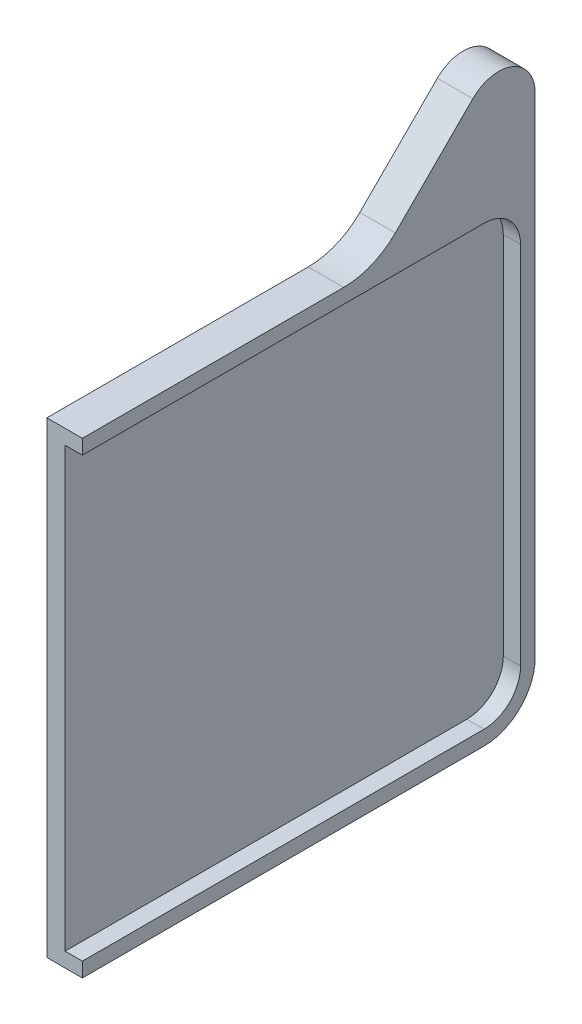
SolidWorks part; units mm, degrees
ref_plane "Front Plane" through (0, 0, 0) normal (0, 0, 1) x (1, 0, 0)
ref_plane "Top Plane" through (0, 0, 0) normal (0, 1, 0) x (1, 0, 0)
ref_plane "Right Plane" through (0, 0, 0) normal (1, 0, 0) x (0, 0, -1)
sketch "Sketch1" plane through (35.1028, 0, 0) normal (-1, 0, 0) x (0, 0, 1)
  line L0 (-114.3, 38.1) -> (-114.3, -38.1)
  line L1 (-114.3, 38.1) -> (-184.15, 38.1)
  line L2 (-190.5, 31.75) -> (-190.5, -31.75)
  line L3 (-184.15, -38.1) -> (-114.3, -38.1)
  line L4 (190.5, -31.75) -> (190.5, 31.75)
  line L5 (184.15, 38.1) -> (-184.15, 38.1)
  line L6 (-190.5, 31.75) -> (-190.5, -31.75)
  line L7 (-184.15, -38.1) -> (184.15, -38.1)
  line L8 (190.5, -31.75) -> (190.5, 31.75) construction
  line L9 (184.15, 38.1) -> (-184.15, 38.1) construction
  line L10 (-190.5, 31.75) -> (-190.5, -31.75) construction
  line L11 (-184.15, -38.1) -> (184.15, -38.1) construction
  arc A0 (-190.5, -31.75) -> (-184.15, -38.1) centre (-184.15, -31.75) ccw
  arc A1 (-190.5, 31.75) -> (-184.15, 38.1) centre (-184.15, 31.75) cw
  arc A4 (184.15, -38.1) -> (190.5, -31.75) centre (184.15, -31.75) ccw
  arc A5 (190.5, 31.75) -> (184.15, 38.1) centre (184.15, 31.75) ccw
  arc A6 (-184.15, 38.1) -> (-190.5, 31.75) centre (-184.15, 31.75) ccw
  arc A7 (-190.5, -31.75) -> (-184.15, -38.1) centre (-184.15, -31.75) ccw
  arc A8 (184.15, -38.1) -> (190.5, -31.75) centre (184.15, -31.75) ccw construction
  arc A9 (190.5, 31.75) -> (184.15, 38.1) centre (184.15, 31.75) ccw construction
  arc A10 (-184.15, 38.1) -> (-190.5, 31.75) centre (-184.15, 31.75) ccw construction
  arc A11 (-190.5, -31.75) -> (-184.15, -38.1) centre (-184.15, -31.75) ccw construction
  dimension "D2" = 76.2
  dimension "D1" = 0
extrude "Boss-Extrude1" add sketch "Sketch1" along normal blind 3.175 contours L0 L3 A0 L2 A1 L1
ref_plane "Plane1" through (35.1028, 38.1, -184.15) normal (0, 0, -1) x (-1, 0, 0)
sketch "Sketch4" plane through (31.9278, 0, 0) normal (-1, 0, 0) x (0, 0, 1)
  line L4 (-114.3, 38.1) -> (-184.15, 38.1)
  line L5 (-190.5, 31.75) -> (-190.5, -31.75)
  line L6 (-184.15, -38.1) -> (-114.3, -38.1)
  line L7 (-114.3, -38.1) -> (-114.3, 38.1)
  line L8 (-114.3, 38.1) -> (-184.15, 38.1)
  line L9 (-190.5, 31.75) -> (-190.5, -31.75)
  line L10 (-184.15, -38.1) -> (-114.3, -38.1)
  line L11 (-114.3, -38.1) -> (-114.3, 38.1) construction
  arc A2 (-184.15, 38.1) -> (-190.5, 31.75) centre (-184.15, 31.75) ccw
  arc A3 (-190.5, -31.75) -> (-184.15, -38.1) centre (-184.15, -31.75) ccw
  arc A4 (-184.15, 38.1) -> (-190.5, 31.75) centre (-184.15, 31.75) ccw
  arc A5 (-190.5, -31.75) -> (-184.15, -38.1) centre (-184.15, -31.75) ccw
  dimension "D1" = 0
extrude "Extrude-Thin1" add sketch "Sketch4" against normal up to surface (6.1722 mm away) thin thin type one direction wall 2.54
sketch "Sketch5" plane through (31.9278, 0, 0) normal (-1, 0, 0) x (0, 0, 1)
  line L0 (-177.8, 12.7) -> (-120.65, 12.7) construction
  line L1 (-177.8, 15.875) -> (-171.45, 15.875)
  line L2 (-177.8, 9.525) -> (-171.45, 9.525)
  line L3 (-171.45, 15.875) -> (-170.3501, 15.24)
  line L6 (-114.3, 0) -> (-193.04, 0) construction
  line L7 (-114.3, 40.64) -> (-114.3, -40.64) construction
  line L8 (-193.04, 31.75) -> (-193.04, -31.75) construction
  line L9 (-170.3501, 15.24) -> (-128.0999, 15.24)
  line L10 (-128.0999, 15.24) -> (-127, 15.875)
  line L11 (177.8, -15.875) -> (-177.8, -15.875)
  line L12 (-177.8, -22.225) -> (177.8, -22.225)
  line L13 (190.5, -31.75) -> (190.5, 31.75)
  line L14 (184.15, 38.1) -> (-184.15, 38.1)
  line L15 (-190.5, 31.75) -> (-190.5, -31.75)
  line L16 (-184.15, -38.1) -> (184.15, -38.1)
  line L17 (190.5, -31.75) -> (190.5, 31.75) construction
  line L18 (184.15, 38.1) -> (-184.15, 38.1) construction
  line L19 (-190.5, 31.75) -> (-190.5, -31.75) construction
  line L20 (-184.15, -38.1) -> (184.15, -38.1) construction
  line L22 (-177.8, -22.225) -> (177.8, -22.225) construction
  line L23 (177.8, 22.225) -> (-177.8, 22.225)
  line L24 (-177.8, 15.875) -> (177.8, 15.875)
  line L25 (177.8, 22.225) -> (-177.8, 22.225) construction
  line L26 (-177.8, 15.875) -> (177.8, 15.875) construction
  line L27 (-171.45, 9.525) -> (-170.3501, 10.16)
  line L28 (-170.3501, 10.16) -> (-128.0999, 10.16)
  line L29 (-128.0999, 10.16) -> (-127, 9.525)
  line L30 (-127, 15.875) -> (-120.65, 15.875)
  line L31 (-171.45, 15.875) -> (-127, 15.875) construction
  line L32 (-127, 9.525) -> (-120.65, 9.525)
  line L33 (-171.45, 9.525) -> (-127, 9.525) construction
  line L34 (-180.975, -12.7) -> (-180.975, 12.7) construction
  arc A0 (-177.8, 15.875) -> (-177.8, 9.525) centre (-177.8, 12.7) ccw
  arc A1 (-120.65, 9.525) -> (-120.65, 15.875) centre (-120.65, 12.7) ccw
  circle A5 centre (184.15, 31.75) radius 1.5875
  arc A6 (177.8, -22.225) -> (177.8, -15.875) centre (177.8, -19.05) ccw
  arc A7 (-177.8, -15.875) -> (-177.8, -22.225) centre (-177.8, -19.05) ccw
  arc A8 (184.15, -38.1) -> (190.5, -31.75) centre (184.15, -31.75) ccw
  arc A9 (190.5, 31.75) -> (184.15, 38.1) centre (184.15, 31.75) ccw
  arc A10 (-184.15, 38.1) -> (-190.5, 31.75) centre (-184.15, 31.75) ccw
  arc A11 (-190.5, -31.75) -> (-184.15, -38.1) centre (-184.15, -31.75) ccw
  arc A12 (184.15, -38.1) -> (190.5, -31.75) centre (184.15, -31.75) ccw construction
  arc A13 (190.5, 31.75) -> (184.15, 38.1) centre (184.15, 31.75) ccw construction
  arc A14 (-184.15, 38.1) -> (-190.5, 31.75) centre (-184.15, 31.75) ccw construction
  arc A15 (-190.5, -31.75) -> (-184.15, -38.1) centre (-184.15, -31.75) ccw construction
  arc A16 (177.8, -22.225) -> (177.8, -15.875) centre (177.8, -19.05) ccw construction
  arc A18 (177.8, 15.875) -> (177.8, 22.225) centre (177.8, 19.05) ccw
  arc A19 (-177.8, 22.225) -> (-177.8, 15.875) centre (-177.8, 19.05) ccw
  arc A20 (177.8, 15.875) -> (177.8, 22.225) centre (177.8, 19.05) ccw construction
  arc A21 (-177.8, 22.225) -> (-177.8, 15.875) centre (-177.8, 19.05) ccw construction
  circle A22 centre (184.15, 31.75) radius 1.5875 construction
  circle A23 centre (184.15, 0) radius 1.5875
  circle A24 centre (184.15, 0) radius 1.5875 construction
  circle A25 centre (184.15, -31.75) radius 1.5875
  circle A26 centre (184.15, -31.75) radius 1.5875 construction
  circle A27 centre (120.65, -31.75) radius 1.5875
  circle A28 centre (120.65, -31.75) radius 1.5875 construction
  circle A29 centre (120.65, 0) radius 1.5875
  circle A30 centre (120.65, 0) radius 1.5875 construction
  circle A31 centre (120.65, 31.75) radius 1.5875
  circle A32 centre (120.65, 31.75) radius 1.5875 construction
  circle A33 centre (-184.15, 31.75) radius 1.5875
  circle A34 centre (-184.15, 31.75) radius 1.5875 construction
  circle A35 centre (-174.625, 31.75) radius 1.5875
  circle A36 centre (-174.625, 31.75) radius 1.5875 construction
  circle A37 centre (-174.625, -31.75) radius 1.5875
  circle A38 centre (-174.625, -31.75) radius 1.5875 construction
  circle A39 centre (-184.15, -31.75) radius 1.5875
  circle A40 centre (-184.15, -31.75) radius 1.5875 construction
  point P2 (-149.225, 12.7)
  point P20 (-180.975, 12.7)
  point P21 (-117.475, 12.7)
  point P79 (0, 0)
  point P80 (-180.975, 0)
  point P81 (0, 0)
  point P82 (-180.975, 19.05)
  dimension "D3" = 6.35
  dimension "D1" = 63.5
  dimension "D16" = 6.35
  dimension "D17" = 30
  dimension "D18" = 30
  dimension "D19" = 25.4
  dimension "D20" = 0.635
  dimension "D2" = 0
  dimension "D4" = 0
  dimension "D5" = 0
  dimension "D6" = 0
  dimension "D7" = 0
  dimension "D8" = 0
  dimension "D9" = 0
  dimension "D10" = 0
  dimension "D11" = 0
  dimension "D12" = 0
  dimension "D13" = 0
  dimension "D14" = 0
  dimension "D15" = 0
extrude "Boss-Extrude2" add sketch "Sketch5" along normal blind 2.9972 contours A0 L2 L27 L28 L29 L32 A1 L30 L10 L9 L3 L1
fillet "Fillet1" radius 3.175 4 edges at (30.4292, 9.525, -171.45) (30.4292, 9.525, -127) (30.4292, 15.875, -127) (30.4292, 15.875, -171.45)
mirror "Mirror1" about plane through (0, 0, 0) normal (0, 1, 0) of "Fillet1", "Boss-Extrude2"
sketch "Sketch6" plane through (31.9278, 0, 0) normal (-1, 0, 0) x (0, 0, 1)
  line L0 (-193.04, 31.75) -> (-193.04, 53.34)
  line L1 (-182.1999, 57.8301) -> (-168.7295, 44.3597)
  line L2 (-114.3, 40.64) -> (-184.15, 40.64) construction
  line L7 (-114.3, -40.64) -> (-114.3, 40.64)
  line L8 (-114.3, 40.64) -> (-184.15, 40.64)
  line L9 (-193.04, 31.75) -> (-193.04, -31.75)
  line L10 (-184.15, -40.64) -> (-114.3, -40.64)
  line L11 (-114.3, -40.64) -> (-114.3, 40.64) construction
  line L12 (-114.3, 40.64) -> (-184.15, 40.64)
  line L13 (-193.04, 31.75) -> (-193.04, -31.75)
  line L14 (-184.15, -40.64) -> (-114.3, -40.64)
  arc A0 (-193.04, 53.34) -> (-182.1999, 57.8301) centre (-186.69, 53.34) cw
  arc A1 (-168.7295, 44.3597) -> (-159.7492, 40.64) centre (-159.7492, 53.34) ccw
  arc A4 (-184.15, 40.64) -> (-193.04, 31.75) centre (-184.15, 31.75) ccw
  arc A5 (-193.04, -31.75) -> (-184.15, -40.64) centre (-184.15, -31.75) ccw
  arc A6 (-184.15, 40.64) -> (-193.04, 31.75) centre (-184.15, 31.75) ccw
  arc A7 (-193.04, -31.75) -> (-184.15, -40.64) centre (-184.15, -31.75) ccw
  point P14 (-193.04, 31.278)
  arc M10 (-184.15, 40.64) -> (-193.04, 31.75) centre (-184.15, 31.75) ccw
  dimension "D1" = 6.35
  dimension "D2" = 12.7
  dimension "D3" = 45
  dimension "D5" = 12.7
  dimension "D4" = 0
extrude "Boss-Extrude3" add sketch "Sketch6" against normal up to surface (6.1722 mm away) contours A1 L1 A0 L0 L12 M10 region at (31.9278, 47.7442, -182.964) up to face at (38.1, 0, -163.9327)
